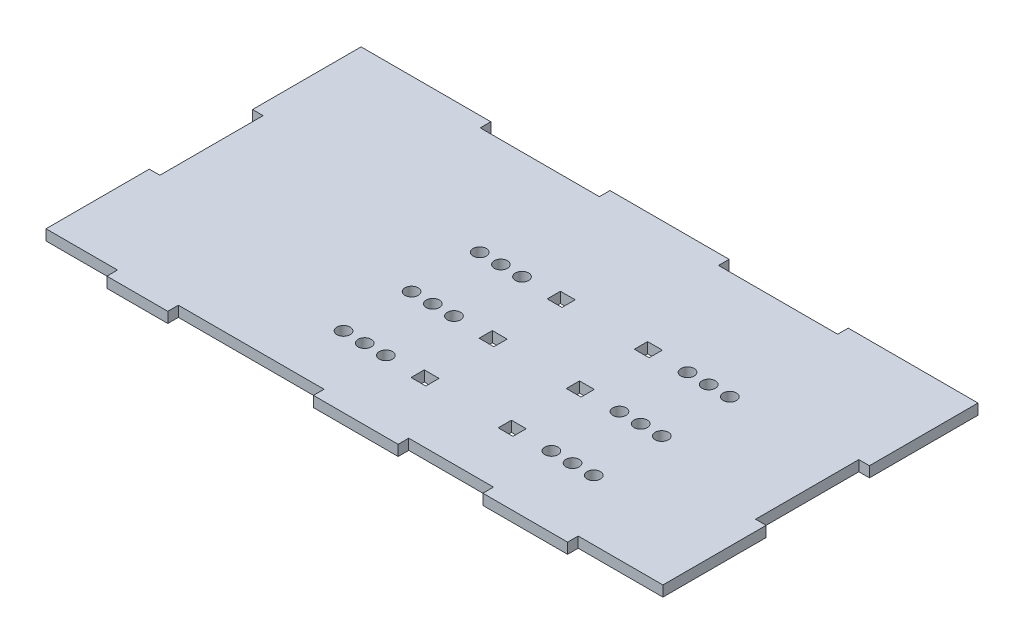
SolidWorks part; units mm, degrees
ref_plane "Front Plane" through (0, 0, 0) normal (0, 0, 1) x (1, 0, 0)
ref_plane "Top Plane" through (0, 0, 0) normal (0, 1, 0) x (1, 0, 0)
ref_plane "Right Plane" through (0, 0, 0) normal (1, 0, 0) x (0, 0, -1)
sketch "Sketch1" plane through (0, 0, 0) normal (0, 1, 0) x (1, 0, 0)
  line L1 (0, 0) -> (225, 0)
  line L2 (0, 0) -> (0, 115)
  line L3 (0, 115) -> (225, 115)
  line L4 (225, 0) -> (225, 115)
  dimension "D1" = 225
  dimension "D2" = 115
extrude "Boss-Extrude1" add sketch "Sketch1" along normal blind 4
ref_plane "Plane1" through (197.5, -108, -1) normal (0, 0, -1) x (-1, 0, 0)
sketch "Sketch3" plane through (0, 4, 0) normal (0, 1, 0) x (1, 0, 0)
  line L1 (152.09, 76.7) -> (146.51, 76.7)
  line L2 (152.09, 76.7) -> (152.09, 71.7)
  line L3 (152.09, 71.7) -> (146.51, 71.7)
  line L4 (146.51, 76.7) -> (146.51, 71.7)
  line L5 (119.17, 71.7) -> (113.59, 71.7)
  line L6 (119.17, 76.7) -> (113.59, 76.7)
  line L7 (113.59, 76.7) -> (113.59, 71.7)
  line L8 (119.17, 76.7) -> (119.17, 71.7)
  line L9 (119.17, 45.99) -> (113.59, 45.99)
  line L10 (119.17, 50.99) -> (113.59, 50.99)
  line L11 (113.59, 50.99) -> (113.59, 45.99)
  line L12 (119.17, 50.99) -> (119.17, 45.99)
  line L13 (119.17, 20.28) -> (113.59, 20.28)
  line L14 (119.17, 25.28) -> (113.59, 25.28)
  line L15 (113.59, 25.28) -> (113.59, 20.28)
  line L16 (119.17, 25.28) -> (119.17, 20.28)
  line L17 (152.09, 45.99) -> (146.51, 45.99)
  line L18 (152.09, 50.99) -> (146.51, 50.99)
  line L19 (146.51, 50.99) -> (146.51, 45.99)
  line L20 (152.09, 50.99) -> (152.09, 45.99)
  line L21 (152.09, 20.28) -> (146.51, 20.28)
  line L22 (152.09, 25.28) -> (146.51, 25.28)
  line L23 (146.51, 25.28) -> (146.51, 20.28)
  line L24 (152.09, 25.28) -> (152.09, 20.28)
  line L26 (146.51, 76.7) -> (119.17, 76.7) construction
  line L29 (146.51, 50.99) -> (119.17, 50.99) construction
  line L30 (146.51, 25.28) -> (119.17, 25.28) construction
  line L31 (180.09, 25.28) -> (192.09, 25.28) construction
  line L32 (180.09, 50.99) -> (192.09, 50.99) construction
  line L33 (180.09, 76.7) -> (192.09, 76.7) construction
  line L34 (85.59, 25.28) -> (71.09, 25.28) construction
  line L35 (85.59, 50.99) -> (71.09, 50.99) construction
  line L36 (85.59, 76.7) -> (71.09, 76.7) construction
  line L42 (225, 115) -> (0, 115) construction
  circle A0 centre (180.09, 74.2) radius 2.5
  circle A1 centre (172.09, 74.2) radius 2.5
  circle A2 centre (164.09, 74.2) radius 2.5
  circle A3 centre (101.59, 74.2) radius 2.5
  circle A4 centre (93.59, 74.2) radius 2.5
  circle A5 centre (85.59, 74.2) radius 2.5
  circle A6 centre (101.59, 48.49) radius 2.5
  circle A7 centre (93.59, 48.49) radius 2.5
  circle A8 centre (85.59, 48.49) radius 2.5
  circle A9 centre (101.59, 22.78) radius 2.5
  circle A10 centre (93.59, 22.78) radius 2.5
  circle A11 centre (85.59, 22.78) radius 2.5
  circle A12 centre (180.09, 48.49) radius 2.5
  circle A13 centre (172.09, 48.49) radius 2.5
  circle A14 centre (164.09, 48.49) radius 2.5
  circle A15 centre (180.09, 22.78) radius 2.5
  circle A16 centre (172.09, 22.78) radius 2.5
  circle A17 centre (164.09, 22.78) radius 2.5
  text T0 "ODrive 3" font "Century Gothic" height 5
  text T1 "ODrive 2" font "Zag Bold" height 5
  text T2 "ODrive 1" font "Zag Bold" height 5
  text T3 "M1" font "Zag Bold" height 5
  text T4 "M1" font "Zag Bold" height 5
  text T5 "M1" font "Zag Bold" height 5
  text T6 "M0" font "Zag Bold" height 5
  text T7 "M0" font "Zag Bold" height 5
  text T8 "M0" font "Zag Bold" height 5
  point P42 (152.09, 74.2)
  point P78 (124.19, 69.99)
  dimension "D1" = 5
  dimension "D5" = 5.58
  dimension "D6" = 5
  dimension "D9" = 12
  dimension "D11" = 14.5
  dimension "D13" = 40.8
  dimension "D14" = 12
  dimension "D15" = 12
  dimension "D2" = 3
  dimension "D3" = 2
  dimension "D4" = 3
  dimension "D7" = 2
  dimension "D8" = 3
  dimension "D10" = 3
  dimension "D12" = 3
extrude "Cut-Extrude2" cut sketch "Sketch3" against normal blind 10 contours A15 | A16 | A17 | L24 L22 L23 L21 | A12 | A13 | A14 | L20 L18 L19 L17 | A0 | A1 | A2 | L1 L4 L3 L2 | L8 L6 L7 L5 | L12 L10 L11 L9 | L16 L14 L15 L13 | A9 | A10 | A11 | A8 | A7 | A6 | A3 | A4 | A5 region at (149.3, 4, -74.2) region at (116.38, 4, -74.2) region at (116.38, 4, -48.49) region at (116.38, 4, -22.78) region at (149.3, 4, -48.49) region at (149.3, 4, -22.78) region at (180.09, 4, -74.2) region at (172.09, 4, -74.2) region at (164.09, 4, -74.2) region at (101.59, 4, -74.2) region at (93.59, 4, -74.2) region at (85.59, 4, -74.2) region at (101.59, 4, -48.49) region at (93.59, 4, -48.49) region at (85.59, 4, -48.49) region at (101.59, 4, -22.78) region at (93.59, 4, -22.78) region at (85.59, 4, -22.78) region at (180.09, 4, -48.49) region at (172.09, 4, -48.49) region at (164.09, 4, -48.49) region at (180.09, 4, -22.78) region at (172.09, 4, -22.78) region at (164.09, 4, -22.78)
sketch "Sketch4" plane through (0, 4, 0) normal (0, 1, 0) x (1, 0, 0)
  line L0 (0, 115) -> (0, 0) construction
  line L5 (0, 0) -> (-4, 0)
  line L6 (0, 0) -> (0, 39)
  line L7 (0, 39) -> (-4, 39)
  line L8 (-4, 0) -> (-4, 39)
  line L9 (0, 117) -> (-4, 117)
  line L10 (0, 117) -> (0, 78)
  line L11 (0, 78) -> (-4, 78)
  line L12 (-4, 117) -> (-4, 78)
  dimension "D1" = 39
  dimension "D2" = 39
  dimension "D3" = 39
  dimension "D4" = 4
extrude "Boss-Extrude2" add sketch "Sketch4" against normal blind 4
sketch "Sketch5" plane through (0, 4, 0) normal (0, 1, 0) x (1, 0, 0)
  line L0 (135, 115) -> (135, 119)
  line L1 (225, 115) -> (180, 115)
  line L2 (225, 115) -> (225, 119)
  line L3 (225, 119) -> (180, 119)
  line L4 (180, 115) -> (180, 119)
  line L5 (135, 115) -> (90, 115)
  line L6 (90, 115) -> (90, 119)
  line L7 (135, 119) -> (90, 119)
  line L8 (45, 115) -> (45, 119)
  line L9 (45, 115) -> (0, 115)
  line L10 (0, 115) -> (0, 119)
  line L11 (45, 119) -> (0, 119)
  dimension "D1" = 45
  dimension "D2" = 4
  dimension "D3" = 3
extrude "Boss-Extrude3" add sketch "Sketch5" against normal blind 4
pattern_linear "LPattern1" count 2 spacing 229 along (1, 0, 0) of "Boss-Extrude2"
sketch "Sketch6" plane through (0, 4, 0) normal (0, 1, 0) x (1, 0, 0)
  line L8 (-4, 0) -> (229, 0) construction
  line L9 (23, 0) -> (46, 0)
  line L10 (23, 0) -> (23, -4)
  line L11 (23, -4) -> (46, -4)
  line L12 (46, 0) -> (46, -4)
  dimension "D1" = 23
  dimension "D2" = 4
  dimension "D3" = 23
extrude "Boss-Extrude4" add sketch "Sketch6" against normal blind 4
sketch "Sketch7" plane through (0, 4, 0) normal (0, 1, 0) x (1, 0, 0)
  line L0 (-4, 0) -> (69, 0) construction
  line L1 (46, 0) -> (229, 0) construction
  line L2 (165, 0) -> (165, -4)
  line L3 (101, 0) -> (133, 0)
  line L4 (101, 0) -> (101, -4)
  line L5 (101, -4) -> (133, -4)
  line L6 (133, 0) -> (133, -4)
  line L7 (165, 0) -> (197, 0)
  line L8 (197, 0) -> (197, -4)
  line L9 (165, -4) -> (197, -4)
  dimension "D1" = 73
  dimension "D2" = 32
  dimension "D3" = 4
  dimension "D4" = 32
  dimension "D5" = 2
extrude "Boss-Extrude5" add sketch "Sketch7" against normal blind 4
sketch "Sketch8" plane through (0, 4, 0) normal (0, 1, 0) x (1, 0, 0)
  line L0 (-4, 117) -> (-4, 78) construction
  line L1 (0, 117) -> (-4, 117)
  line L2 (0, 117) -> (0, 119)
  line L3 (0, 119) -> (-4, 119)
  line L4 (-4, 117) -> (-4, 119)
  line L5 (45, 119) -> (0, 119) construction
  line L7 (225, 119) -> (229, 119)
  line L8 (225, 119) -> (225, 117)
  line L9 (225, 117) -> (229, 117)
  line L10 (229, 119) -> (229, 117)
extrude "Boss-Extrude6" add sketch "Sketch8" against normal blind 4
equation "\"Dikte\"= 4"
equation "\"D1@Sketch1\"=225"
equation "\"D15@Sketch3\"=\"D14@Sketch3\""
